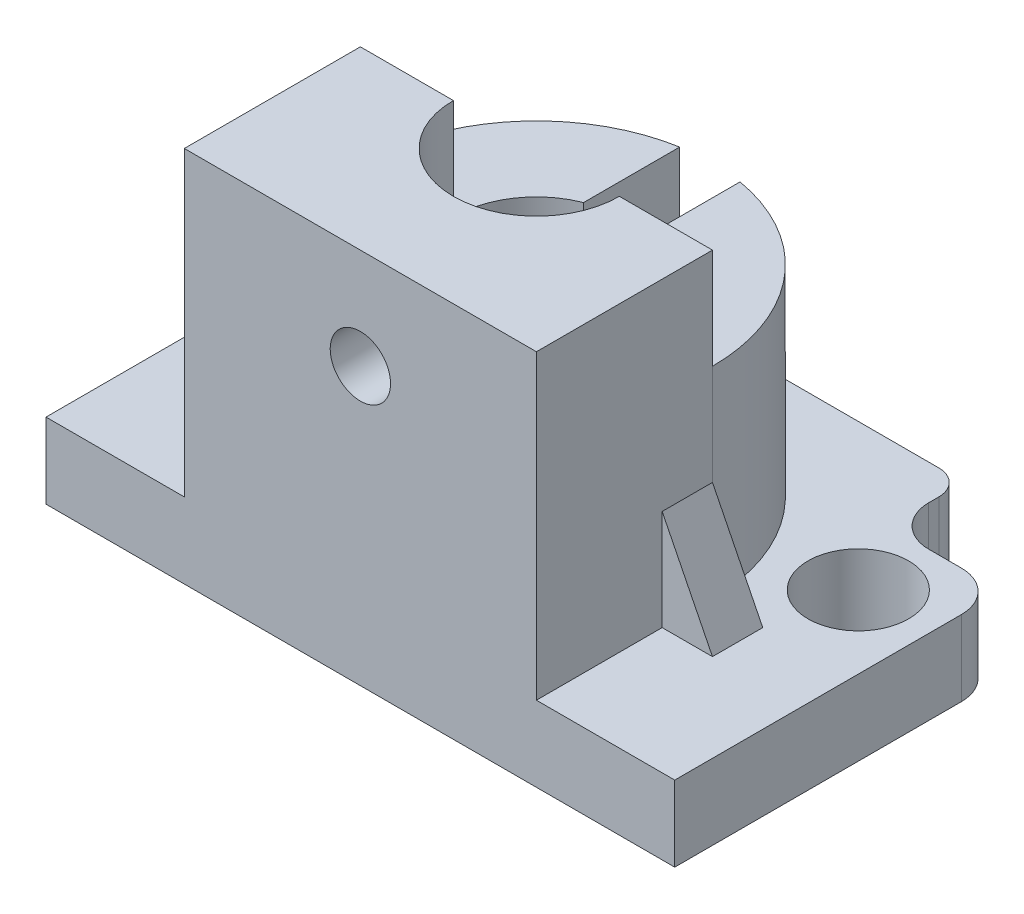
SolidWorks part; units mm, degrees
ref_plane "前视基准面" through (0, 0, 0) normal (0, 0, 1) x (1, 0, 0)
ref_plane "上视基准面" through (0, 0, 0) normal (0, 1, 0) x (1, 0, 0)
ref_plane "右视基准面" through (0, 0, 0) normal (1, 0, 0) x (0, 0, -1)
other "Configuration Table"
sketch "草图1" plane through (0, 0, 0) normal (0, 1, 0) x (1, 0, 0)
  line L0 (-62.5, 0) -> (62.5, 0)
  line L1 (0, 0) -> (0, 80) construction
  line L2 (-62.5, 0) -> (-62.5, 65)
  line L3 (-62.5, 65) -> (-40, 65)
  line L4 (-40, 65) -> (-40, 80)
  line L5 (-40, 80) -> (40, 80)
  line L6 (40, 65) -> (40, 80)
  line L7 (62.5, 65) -> (40, 65)
  line L8 (62.5, 0) -> (62.5, 65)
  circle A0 centre (-48, 51) radius 10
  circle A1 centre (48, 51) radius 10
  dimension "D5" = 20
  dimension "D6" = 51
  dimension "D7" = 96
  dimension "D1" = 80
  dimension "D2" = 65
  dimension "D3" = 62.5
  dimension "D4" = 40
extrude "凸台-拉伸1" add sketch "草图1" along normal blind 15 contours A1 | A0 | L5 L6 L7 L8 L0 L2 L3 L4 region at (-48, 0, -51) region at (48, 0, -51)
fillet "圆角1" radius 5 2 edges at (40, 7.5, -80) (-40, 7.5, -80)
fillet "圆角2" radius 8 4 edges at (-62.5, 7.5, -65) (62.5, 7.5, -65) (-40, 7.5, -65) (40, 7.5, -65)
sketch "草图3" plane through (0, 15, 0) normal (0, 1, 0) x (1, 0, 0)
  line L0 (0, -11.4359) -> (0, 85.5998) construction
  line L1 (-35, 0) -> (-35, 35)
  line L2 (-62.5, 0) -> (62.5, 0) construction
  line L3 (35, 0) -> (35, 35)
  line L4 (-35, 0) -> (35, 0)
  arc A0 (35, 35) -> (-35, 35) centre (0, 35) ccw
  circle A1 centre (0, 35) radius 16.5
  dimension "D3" = 33
  dimension "D1" = 70
  dimension "D2" = 35
extrude "凸台-拉伸2" add sketch "草图3" along normal blind 60
ref_plane "基准面1" through (0, 0, -30) normal (0, 0, 1) x (1, 0, 0)
sketch "草图4" plane through (0, 0, -30) normal (0, 0, 1) x (1, 0, 0)
  line L0 (-35, 35) -> (-45, 15)
  line L1 (-35, 75) -> (-35, 15) construction
  line L2 (-62.5, 15) -> (-35, 15) construction
  dimension "D1" = 20
  dimension "D2" = 10
rib "筋1" sketch "草图4" sketch "草图4" thickness 10 extrusion direction parallel to sketch draft on no parameters "D1"=10
mirror "镜向1" about plane through (0, 0, 0) normal (1, 0, 0) of "筋1"
sketch "草图5" plane through (0, 75, 0) normal (0, 1, 0) x (1, 0, 0)
  line L1 (-40, 75) -> (40, 75)
  line L2 (-40, 75) -> (-40, 35)
  line L3 (-40, 35) -> (40, 35)
  line L4 (40, 75) -> (40, 35)
  line L5 (-40, 75) -> (40, 35) construction
  line L6 (-40, 35) -> (40, 75) construction
  circle A0 centre (0, 35) radius 16.5 construction
  point P0 (0, 55)
  dimension "D1" = 0
  dimension "D2" = 0
  dimension "D3" = 80
  dimension "D4" = 40
extrude "切除-拉伸1" cut sketch "草图5" against normal blind 20
sketch "草图6" plane through (0, 0, -30) normal (0, 0, 1) x (1, 0, 0)
  line L0 (0, -8.4483) -> (0, 82.1417) construction
  line L1 (-35, 75) -> (35, 75) construction
  line L2 (-6, 55) -> (6, 55)
  line L3 (-6, 55) -> (-6, 40)
  line L4 (-6, 40) -> (6, 40)
  line L5 (6, 55) -> (6, 40)
  line L6 (-6, 55) -> (6, 40) construction
  line L7 (-6, 40) -> (6, 55) construction
  point P3 (0, 47.5)
  dimension "D1" = 15
  dimension "D2" = 12
  dimension "D3" = 20
extrude "切除-拉伸2" cut sketch "草图6" against normal up to next
sketch "草图7" plane through (0, 0, -30) normal (0, 0, 1) x (1, 0, 0)
  line L0 (35, 55) -> (-35, 55) construction
  circle A0 centre (0, 55) radius 6
  dimension "D1" = 12
extrude "切除-拉伸3" cut sketch "草图7" along normal up to next
extrude "切除-拉伸4" cut sketch "草图3<2>" against normal up to next contours L0 A1 | A1 L0 region at (-7.0028, 15, -35) region at (7.0028, 15, -35)
sketch "草图3<2>" plane through (0, 15, 0) normal (0, 1, 0) x (1, 0, 0) same geometry as "草图3"
